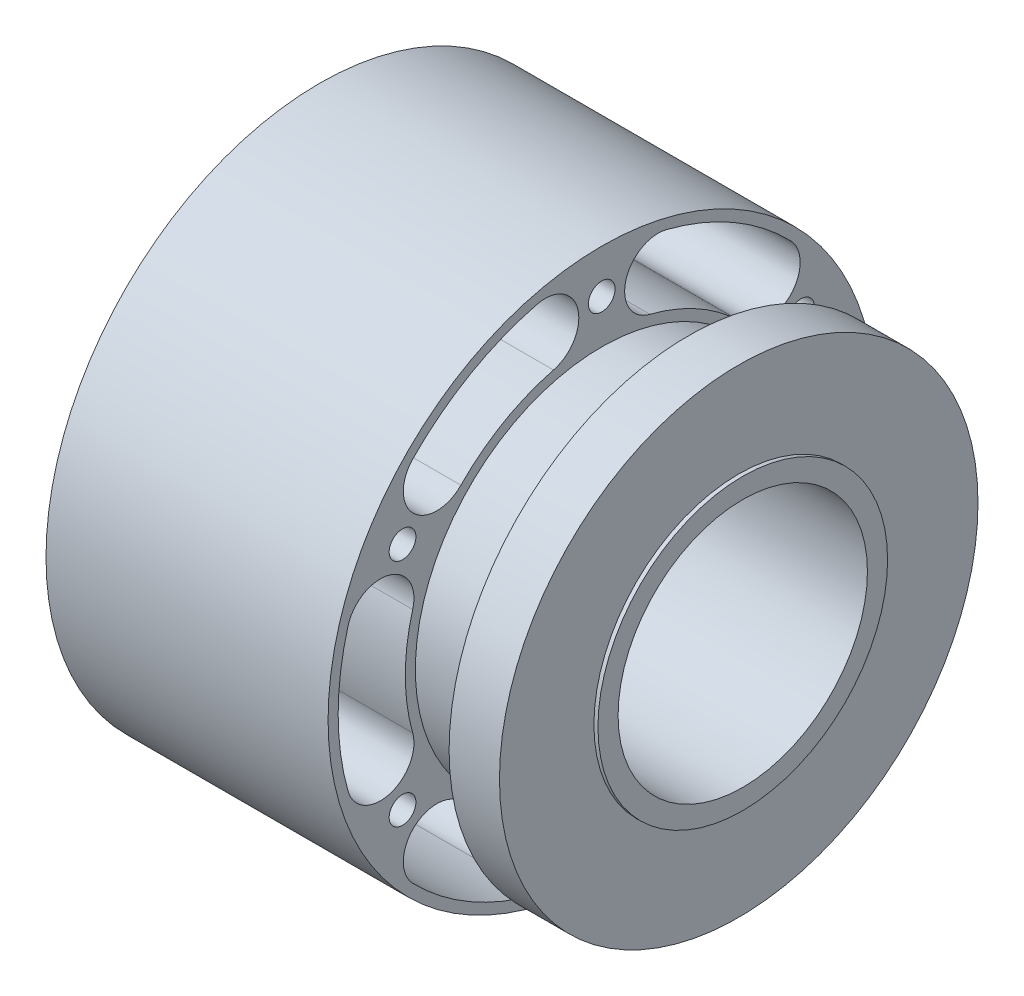
SolidWorks part; units mm, degrees
ref_plane "Front Plane" through (0, 0, 0) normal (1, 0, 0) x (0, 1, 0)
ref_plane "Top Plane" through (0, 0, 0) normal (0, 0, 1) x (0, 1, 0)
ref_plane "Right Plane" through (0, 0, 0) normal (0, 1, 0) x (-1, 0, 0)
sketch "Sketch1" plane through (0, 0, 0) normal (0, 1, 0) x (-1, 0, 0)
  line L0 (0, 68.99) -> (6.35, 68.99)
  line L1 (0, 0) -> (71.12, 0)
  line L2 (0, 0) -> (0, 157.48)
  line L3 (0, 157.48) -> (71.12, 157.48) construction
  line L4 (71.12, 0) -> (71.12, 157.48)
  line L5 (6.35, 68.99) -> (6.35, 149.987)
  line L6 (6.35, 149.987) -> (13.843, 157.48)
  line L7 (63.627, 157.48) -> (71.12, 149.987)
  line L8 (-21.844, 60.325) -> (-21.844, 36.5125)
  line L9 (0, 0) -> (-20.32, 0)
  line L10 (0, 0) -> (0, 46.99)
  line L11 (0, 46.99) -> (-20.32, 46.99)
  line L12 (-20.32, 0) -> (-20.32, 46.99)
  line L13 (71.12, 0) -> (83.82, 0) construction
  line L14 (71.12, 0) -> (71.12, 14.9987) construction
  line L15 (71.12, 14.9987) -> (83.82, 14.9987) construction
  line L16 (83.82, 0) -> (83.82, 14.9987) construction
  line L17 (83.82, 0) -> (96.52, 0) construction
  line L18 (83.82, 0) -> (83.82, 24.13) construction
  line L19 (83.82, 24.13) -> (96.52, 24.13) construction
  line L20 (96.52, 0) -> (96.52, 24.13) construction
  line L21 (-20.32, 0) -> (-35.56, 0)
  line L22 (-20.32, 0) -> (-20.32, 36.5125)
  line L23 (-20.32, 36.5125) -> (-35.56, 36.5125)
  line L24 (-35.56, 0) -> (-35.56, 36.5125)
  line L25 (-21.844, 36.5125) -> (-34.544, 36.5125)
  line L26 (-34.544, 36.5125) -> (-34.544, 60.325)
  line L27 (-34.544, 60.325) -> (-21.844, 60.325)
  line L28 (6.35, 68.99) -> (71.12, 68.99)
  dimension "D1" = 157.48
  dimension "D2" = 71.12
  dimension "D3" = 12.7
  dimension "D4" = 12.7
  dimension "D5" = 14.9987
  dimension "D6" = 24.13
  dimension "D7" = 20.32
  dimension "D8" = 45
  dimension "D9" = 45
  dimension "D11" = 46.99
  dimension "D13" = 36.5125
  dimension "D14" = 132.08
  dimension "D12" = 49.784
  dimension "D16" = 60.325
  dimension "D17" = 12.7
  dimension "D18" = 36.5125
  dimension "D19" = 68.99
  dimension "D15" = 1.016
revolve "Revolve1" add sketch "Sketch1" angle 360 about L1 region at (-35.56, 0, 34.495) region at (10.16, 0, 23.495) region at (27.94, 0, 18.2562)
revolve "Revolve2" add sketch "Sketch1<3>" angle 360 about L1 region at (28.194, 0, 48.4187)
sketch "Sketch1<3>" plane through (0, 0, 0) normal (0, 1, 0) x (-1, 0, 0) same geometry as "Sketch1"
sketch "Sketch2" plane through (-71.12, 0, 0) normal (-1, 0, 0) x (0, -1, 0)
  line L1 (0, -38.1) -> (36.2353, -11.7735)
  line L2 (36.2353, -11.7735) -> (22.3946, 30.8235)
  line L3 (22.3946, 30.8235) -> (-22.3946, 30.8235)
  line L4 (-22.3946, 30.8235) -> (-36.2353, -11.7735)
  line L5 (-36.2353, -11.7735) -> (0, -38.1)
  circle A0 centre (0, 0) radius 38.1
  circle A1 centre (0, 0) radius 68.99
  circle A3 centre (0, 0) radius 30.8235 construction
  circle A5 centre (0, 0) radius 68.99
  dimension "D2" = 76.2
  dimension "D1" = 0
sketch "Sketch3" plane through (-71.12, 0, 0) normal (-1, 0, 0) x (0, -1, 0)
  circle A0 centre (-22.3946, 30.8235) radius 3.3734
  circle A1 centre (22.3946, 30.8235) radius 3.3734
  circle A2 centre (36.2353, -11.7735) radius 3.3734
  circle A3 centre (0, -38.1) radius 3.3734
  circle A4 centre (-36.2353, -11.7735) radius 3.3734
  point P0 (-36.2353, -11.7735)
  point P2 (0, -38.1)
  point P4 (36.2353, -11.7735)
  point P6 (22.3946, 30.8235)
  point P8 (-22.3946, 30.8235)
  dimension "D1" = 6.7469
extrude "Cut-Extrude1" cut sketch "Sketch3" against normal blind 13.97
sketch "Sketch4" plane through (0, 0, 0) normal (1, 0, 0) x (0, 1, 0)
  line L0 (28.995, -50.2208) -> (57.99, 0)
  line L1 (57.99, 0) -> (28.995, 50.2208)
  line L2 (28.995, 50.2208) -> (-28.995, 50.2208)
  line L3 (-28.995, 50.2208) -> (-57.99, 0)
  line L4 (-57.99, 0) -> (-28.995, -50.2208)
  line L5 (-28.995, -50.2208) -> (28.995, -50.2208)
  circle A0 centre (0, 0) radius 50.2208 construction
  circle A1 centre (0, 0) radius 68.99
  circle A2 centre (0, 0) radius 68.99
  circle A3 centre (28.995, 50.2208) radius 3.3734
  dimension "D3" = 6.7469
  dimension "D2" = 115.98
  dimension "D1" = 0
sketch "Sketch5" plane through (0, 0, 0) normal (1, 0, 0) x (0, 1, 0)
  circle A0 centre (28.995, 50.2208) radius 3.3734 construction
  circle A1 centre (28.995, 50.2208) radius 3.3734
  circle A2 centre (-28.995, 50.2208) radius 3.3734
  circle A3 centre (-57.99, 0) radius 3.3734
  circle A4 centre (-28.995, -50.2208) radius 3.3734
  circle A5 centre (28.995, -50.2208) radius 3.3734
  circle A6 centre (57.99, 0) radius 3.3734
  point P0 (28.995, -50.2208)
  point P2 (57.99, 0)
  point P4 (28.995, 50.2208)
  point P9 (-28.995, -50.2208)
  point P11 (-57.99, 0)
  point P13 (-28.995, 50.2208)
extrude "Cut-Extrude2" cut sketch "Sketch5" against normal blind 13.97
ref_plane "mid plane" through (-35.56, 0, 0) normal (-1, 0, 0) x (0, 0, 1)
sketch "Sketch6" plane through (0, 0, 0) normal (1, 0, 0) x (0, 1, 0)
  circle A0 centre (0, 0) radius 46.99 construction
  circle A1 centre (0, 0) radius 68.99 construction
  circle A2 centre (28.995, 50.2208) radius 3.3734 construction
  circle A3 centre (-28.995, 50.2208) radius 3.3734 construction
  circle A4 centre (0, 0) radius 46.99
  circle A5 centre (0, 0) radius 68.99
  circle A6 centre (28.995, 50.2208) radius 3.3734
  circle A7 centre (-28.995, 50.2208) radius 3.3734
  circle A8 centre (0, 0) radius 66.45
  circle A9 centre (0, 0) radius 49.53
  circle A10 centre (-15.7803, 55.8016) radius 8.46
  circle A11 centre (15.7803, 55.8016) radius 8.46
  circle A12 centre (0, 0) radius 57.99 construction
  point P0 (-26.0257, 51.8218)
  point P19 (-23.7314, 52.9118)
  point P21 (23.7314, 52.9118)
  point P22 (26.0257, 51.8218)
  dimension "D1" = 2.54
extrude "f hollow" cut sketch "Sketch6" against normal blind 33.02 contours A11 A8 A10 A9 | A10 | A11 region at (0, 0, 58.2955) region at (0, 15.7803, 55.8016) region at (0, -15.7803, 55.8016)
pattern_circular "CirPattern1" count 6 over 360 about axis through (0, 0, 0) along (-1, 0, 0) of "f hollow" reverse direction yes
sketch "Sketch8" plane through (-71.12, 0, 0) normal (-1, 0, 0) x (0, -1, 0)
  line L0 (-40.5513, 55.8141) -> (0, 0)
  line L1 (0, 0) -> (0, 68.99) construction
  line L2 (-38.0237, 54.4958) -> (0, 2.1607)
  line L3 (38.0237, 54.4958) -> (0, 2.1607)
  circle A0 centre (-22.3946, 30.8235) radius 3.3734 construction
  circle A1 centre (0, 0) radius 68.99
  circle A2 centre (0, 0) radius 68.99
  circle A3 centre (22.3946, 30.8235) radius 3.3734 construction
  circle A4 centre (-22.3946, 30.8235) radius 3.3734
  circle A5 centre (22.3946, 30.8235) radius 3.3734
  circle A6 centre (0, 0) radius 38.1
  circle A7 centre (0, 0) radius 66.45
  circle A8 centre (0, 0) radius 36.83
  circle A9 centre (0, 0) radius 39.37
  arc A12 (-34.5699, 56.7497) -> (-35.6701, 51.2564) centre (-32.5878, 53.4958) ccw
  arc A13 (-3.0824, 6.4032) -> (3.0824, 6.4032) centre (0, 8.6426) ccw
  arc A15 (34.5699, 56.7497) -> (35.6701, 51.2564) centre (32.5878, 53.4958) cw
  circle A17 centre (-22.3946, 30.8235) radius 5.9134
  arc A18 (-26.2404, 38.2775) -> (-22.8589, 36.7187) centre (-23.1581, 40.517) ccw
  arc A19 (-19.5682, 36.0178) -> (-16.1812, 35.891) centre (-17.7471, 39.3644) ccw
  arc A20 (-16.9314, 28.5603) -> (-16.4939, 24.8626) centre (-13.4115, 27.102) ccw
  arc A21 (-14.1396, 34.0076) -> (-16.4847, 30.6205) centre (-12.6769, 30.4896) ccw
  arc A22 (16.9314, 28.5603) -> (16.4939, 24.8626) centre (13.4115, 27.102) cw
  arc A23 (14.1396, 34.0076) -> (16.4847, 30.6205) centre (12.6769, 30.4896) cw
  arc A24 (26.2404, 38.2775) -> (22.8589, 36.7187) centre (23.1581, 40.517) cw
  arc A25 (19.5682, 36.0178) -> (16.1812, 35.891) centre (17.7471, 39.3644) cw
  circle A26 centre (22.3946, 30.8235) radius 5.9134
  dimension "D5" = 7.62
  dimension "D3" = 1.27
  dimension "D7" = 1.27
  dimension "D10" = 2.54
extrude "b hollow" cut sketch "Sketch8" against normal blind 33.02 contours A9 L1 A7 A12 L2 A18 A17 A19 | L1 A9 A25 A26 A24 L3 A15 A7 | A13 L1 A8 A21 A17 A20 L2 | L1 A13 L3 A22 A26 A23 A8 region at (-71.12, -15.6698, 51.1666) region at (-71.12, 15.6698, 51.1666) region at (-71.12, -6.679, 23.757) region at (-71.12, 6.679, 23.757)
pattern_circular "CirPattern2" count 5 over 360 about axis through (0, 0, 0) along (-1, 0, 0) of "b hollow" reverse direction yes
sketch "Sketch9" plane through (35.56, 0, 0) normal (1, 0, 0) x (0, 1, 0)
  circle A0 centre (0, 0) radius 31.4325
  circle A1 centre (0, 0) radius 36.5125
  circle A2 centre (0, 0) radius 36.5125
  dimension "D2" = 5.08
  dimension "D1" = 0
extrude "mid hollow" cut sketch "Sketch9" along normal through all from surface contours A0 region at (35.56, 0, 0) starting at face at (-33.02, 0, 55.7447)
equation "\"D9@Sketch1\"=\"D8@Sketch1\""
equation "\"D2@Sketch6\"=\"D1@Sketch6\""
equation "\"D3@Sketch6\"=\"D1@Sketch6\""
equation "\"D7@Sketch8\"=\"D6@Sketch8\"/2"
equation "\"D3@Sketch8\"=\"D2@Sketch8\"/2"
equation "\"D6@Sketch8\"=\"D2@Sketch8\""
equation "\"D19@Sketch1\"=115.98mm-\"D11@Sketch1\""
